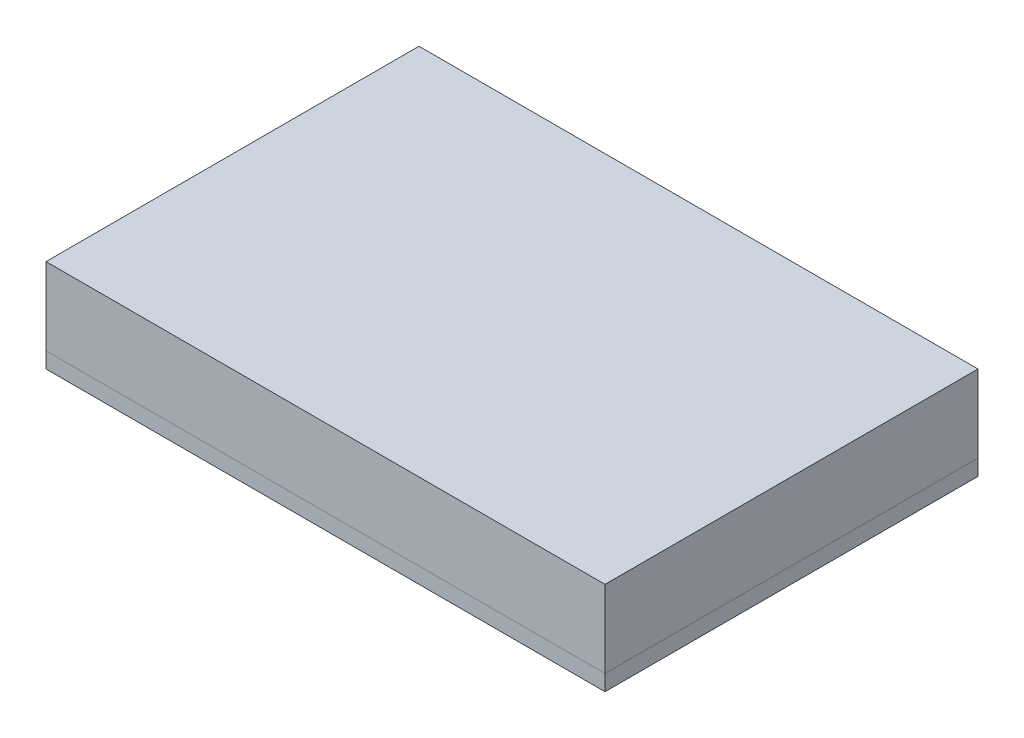
SolidWorks part; units mm, degrees
ref_plane "Front Plane" through (0, 0, 0) normal (0, 0, 1) x (1, 0, 0)
ref_plane "Top Plane" through (0, 0, 0) normal (0, 1, 0) x (1, 0, 0)
ref_plane "Right Plane" through (0, 0, 0) normal (1, 0, 0) x (0, 0, -1)
sketch "Sketch1" plane through (0, 0, 0) normal (0, 1, 0) x (1, 0, 0)
  line L1 (0, 0) -> (60.1, 0)
  line L2 (0, 0) -> (0, 40.1)
  line L3 (0, 40.1) -> (60.1, 40.1)
  line L4 (60.1, 0) -> (60.1, 40.1)
  dimension "D1" = 60.1
  dimension "D2" = 40.1
extrude "Boss-Extrude1" add sketch "Sketch1" along normal blind 1.7
extrude "Boss-Extrude2" add sketch "Sketch1<2>" along normal blind 8.3 from surface separate body starting at face at (30.05, 1.7, -20.05)
sketch "Sketch1<2>" plane through (0, 0, 0) normal (0, 1, 0) x (1, 0, 0) same geometry as "Sketch1"
